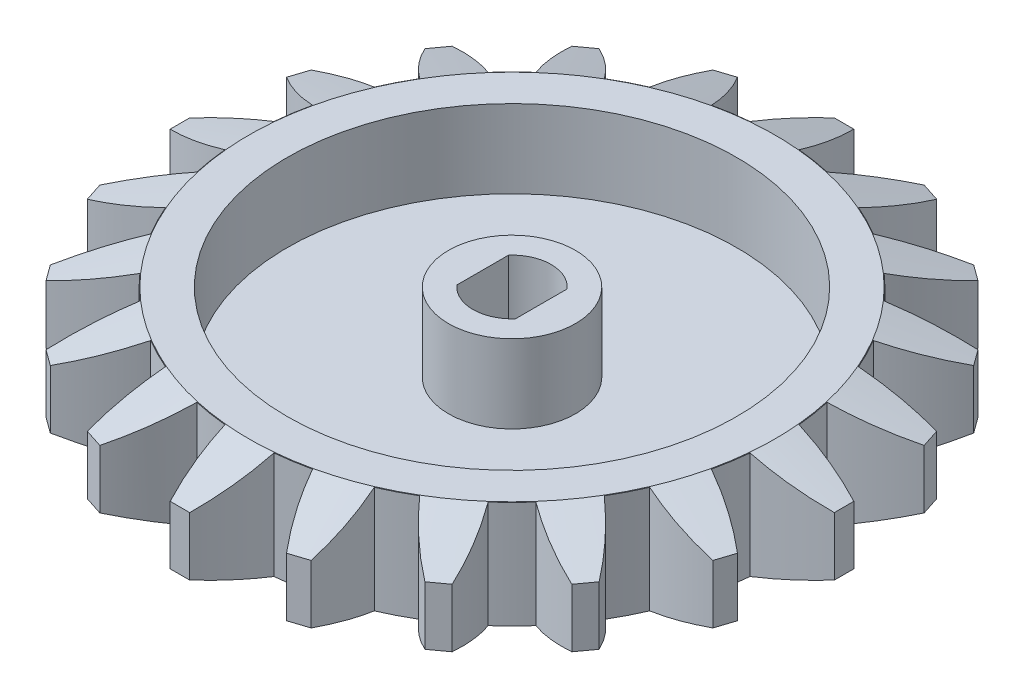
SolidWorks part; units mm, degrees
ref_plane "前视基准面" through (0, 0, 0) normal (0, 0, 1) x (1, 0, 0)
ref_plane "上视基准面" through (0, 0, 0) normal (0, 1, 0) x (1, 0, 0)
ref_plane "右视基准面" through (0, 0, 0) normal (1, 0, 0) x (0, 0, -1)
sketch "草图1" plane through (0, 0, 0) normal (0, 1, 0) x (1, 0, 0)
  circle A0 centre (0, 0) radius 13.5
  dimension "D1" = 27
extrude "凸台-拉伸1" add sketch "草图1" along normal blind 5.5
sketch "草图2" plane through (0, 0, 0) normal (0, 1, 0) x (1, 0, 0)
  line L0 (0, 13.5) -> (0, 17) construction
  line L1 (0.5, 17) -> (-0.5, 17)
  line L2 (0, 15.25) -> (-1, 15.25) construction
  line L3 (0, 13.5) -> (-1.25, 13.5) construction
  arc A0 (1.2542, 13.4416) -> (-1.2542, 13.4416) centre (0, 0) ccw
  arc A1 (-0.5, 17) -> (-1.2542, 13.4416) centre (11.875, 12.5179) ccw
  arc A2 (0.5, 17) -> (1.2542, 13.4416) centre (-11.875, 12.5179) cw
  dimension "D1" = 27
  dimension "D3" = 0.5
  dimension "D4" = 1
extrude "凸台-拉伸2" add sketch "草图2" along normal blind 5.5
sketch "草图3" plane through (0, 5.5, 0) normal (0, 1, 0) x (1, 0, 0)
  circle A0 centre (0, 0) radius 11.5
  circle A1 centre (0, 0) radius 3.25
  dimension "D1" = 6.5
  dimension "D2" = 23
extrude "切除-拉伸1" cut sketch "草图3" against normal blind 4
sketch "草图4" plane through (0, 5.5, 0) normal (0, 1, 0) x (1, 0, 0)
  line L0 (0, 2) -> (0, -2) construction
  line L1 (-1.5, 1.3229) -> (-1.5, -1.3229)
  line L2 (1.5, 1.3229) -> (1.5, -1.3229)
  line L4 (-1.5, 2) -> (-1.5, -2) construction
  line L5 (1.5, 2) -> (1.5, -2) construction
  arc A0 (-1.5, -1.3229) -> (1.5, -1.3229) centre (0, 0) ccw
  arc A1 (1.5, 1.3229) -> (-1.5, 1.3229) centre (0, 0) ccw
  dimension "D1" = 4
  dimension "D2" = 1.5
  dimension "D3" = 1.5
extrude "切除-拉伸2" cut sketch "草图4" against normal up to next
sketch "草图5" plane through (0, 0, 0) normal (0, -1, 0) x (1, 0, 0)
  circle A0 centre (0, 0) radius 2
  dimension "D1" = 4
extrude "切除-拉伸3" cut sketch "草图5" against normal blind 0.2
sketch "草图7" plane through (0, 0, 0) normal (1, 0, 0) x (0, 0, -1)
  line L0 (-0.0292, 0) -> (13.4708, 0) construction
  line L1 (-13.5, 0) -> (13.4416, 0) construction
  line L2 (13.4708, 0) -> (17.9708, 0)
  line L3 (17.9708, 0) -> (17.9708, 1.5938)
  line L4 (17.9708, 1.5938) -> (13.4708, 0)
  line L5 (17, 0) -> (17, 1.25) construction
  line L6 (17, 5.5) -> (17, 0) construction
  line L7 (-0.0292, 0) -> (-0.0292, 2.75) construction
  line L8 (-0.0292, 2.75) -> (3.2353, 2.75) construction
  line L9 (13.4708, 5.5) -> (17.9708, 5.5)
  line L10 (17.9708, 5.5) -> (17.9708, 3.9062)
  line L11 (17.9708, 3.9062) -> (13.4708, 5.5)
  dimension "D1" = 13.5
  dimension "D2" = 4.5
  dimension "D3" = 1.25
  dimension "D4" = 2.75
revolve "切除-旋转3" cut sketch "草图7" angle 360 about L7
pattern_circular "阵列(圆周)2" count 20 over 360 about axis through (0, 5.5, 0) along (0, -1, 0) of "凸台-拉伸2", "切除-旋转3"
